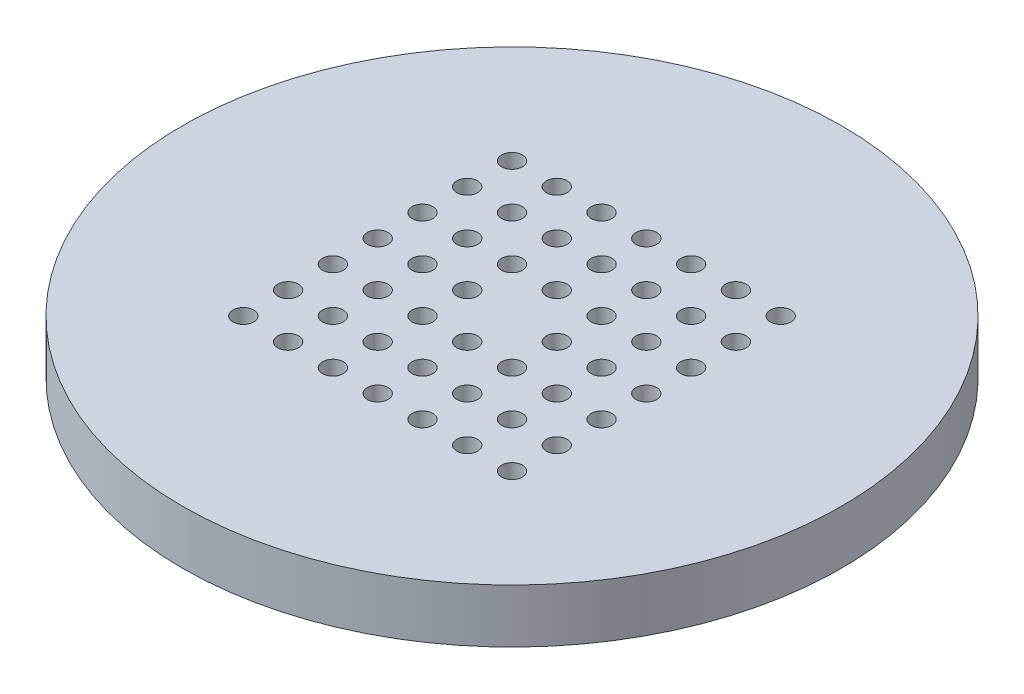
SolidWorks part; units mm, degrees
ref_plane "Front Plane" through (0, 0, 0) normal (0, 0, 1) x (1, 0, 0)
ref_plane "Top Plane" through (0, 0, 0) normal (0, 1, 0) x (1, 0, 0)
ref_plane "Right Plane" through (0, 0, 0) normal (1, 0, 0) x (0, 0, -1)
ref_axis "Axial" through (0, -55, 0) along (0, 1, 0)
sketch "Sketch1" plane through (0, 0, 0) normal (0, 1, 0) x (1, 0, 0)
  circle A0 centre (0, 0) radius 23.368
  dimension "D1" = 46.736
extrude "Billet" add sketch "Sketch1" along normal blind 3.81
sketch "Sketch2" plane through (0, 0, 0) normal (0, 1, 0) x (1, 0, 0)
  line L0 (0, 18.6449) -> (0, -20.0163) construction
  line L1 (-17.698, 0) -> (15.8694, 0) construction
  circle A0 centre (9.525, 9.525) radius 0.7366
  dimension "D1" = 1.4732
  dimension "D2" = 9.525
  dimension "D3" = 9.525
extrude "First Lox Hole" cut sketch "Sketch2" against normal through all and the other way through all contours A0
chamfer "Braising Chamfer" distance 0.254 angle 45 1 edges at (9.525, 0, -8.7884)
pattern_linear "Lox Hole Pattern" count 7 spacing 3.175 along (-1, 0, 0) count 7 spacing 3.175 along (0, 0, 1) skipping (3, 3) of "First Lox Hole", "Braising Chamfer"
sketch "Sketch3" plane through (0, 0, 0) normal (0, -1, 0) x (1, 0, 0)
  line L0 (0, 21.0611) -> (0, -20.7325) construction
  line L1 (-20.4368, 0) -> (21.7511, 0) construction
  circle A0 centre (-19.05, 0) radius 1.27
  dimension "D1" = 2.54
  dimension "D2" = 19.05
extrude "Dowel Hole 1" cut sketch "Sketch3" against normal blind 1.27
pattern_linear "Dowel Hole 2" count 2 spacing 38.1 along (1, 0, 0) of "Dowel Hole 1"
